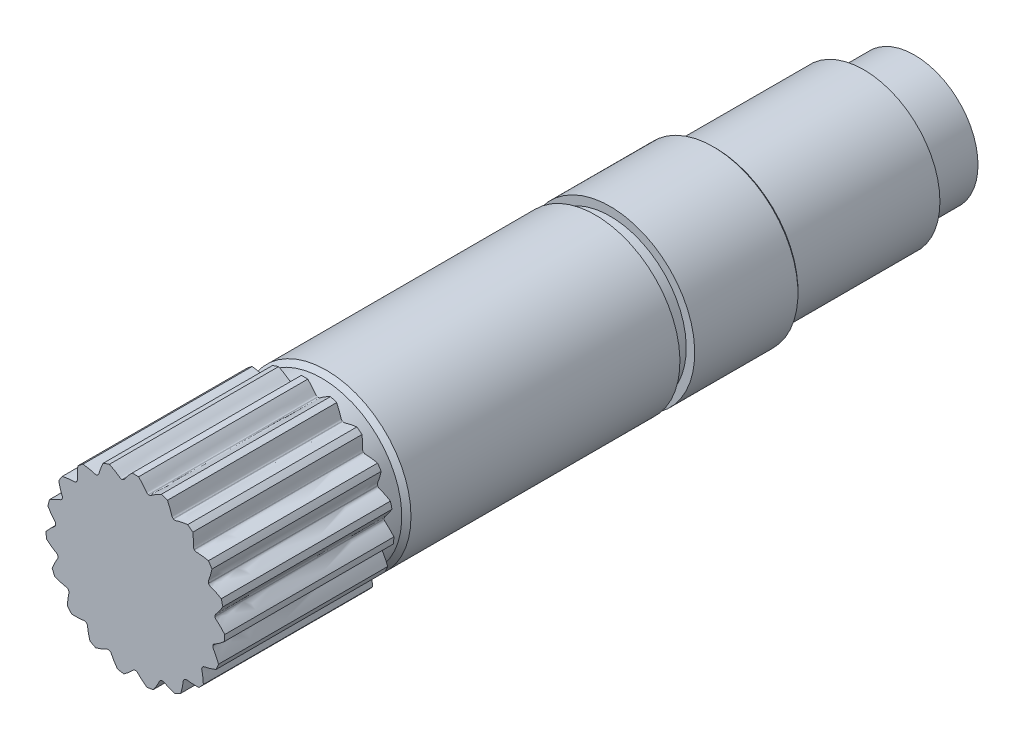
SolidWorks part; units mm, degrees
material "Alloy Steel"
ref_plane "Front Plane" through (0, 0, 0) normal (0, 0, 1) x (1, 0, 0)
ref_plane "Top Plane" through (0, 0, 0) normal (0, 1, 0) x (1, 0, 0)
ref_plane "Right Plane" through (0, 0, 0) normal (1, 0, 0) x (0, 0, -1)
sketch "Sketch12" plane through (0, 0, 0) normal (0, 0, 1) x (1, 0, 0)
  circle A0 centre (0, 0) radius 10
  dimension "D1" = 20
extrude "Shaft" add sketch "Sketch12" along normal mid plane 43
sketch "Sketch13" plane through (0, 0, 21.5) normal (0, 0, 1) x (1, 0, 0)
  circle A0 centre (0, 0) radius 9.4556
  dimension "D1" = 18.9113
extrude "Motor side relief" add sketch "Sketch13" along normal blind 1.587
sketch "Sketch14" plane through (0, 0, -21.5) normal (0, 0, -1) x (-1, 0, 0)
  circle A0 centre (0, 0) radius 8.3981
  dimension "D1" = 16.7963
sketch "Sketch15" plane through (0, 0, 23.087) normal (0, 0, 1) x (1, 0, 0)
  line L0 (5.7898, -7.4758) -> (5.8078, -7.4618)
  line L1 (5.8078, -7.4618) -> (5.8257, -7.4478)
  line L2 (7.9035, -5.1908) -> (7.9159, -5.1717)
  line L3 (7.9159, -5.1717) -> (7.9284, -5.1527)
  line L4 (9.1607, -2.3432) -> (9.1663, -2.3212)
  line L5 (9.1663, -2.3212) -> (9.1719, -2.2992)
  line L6 (9.4252, 0.7582) -> (9.4233, 0.7808)
  line L7 (9.4233, 0.7808) -> (9.4214, 0.8035)
  line L8 (8.6683, 3.7775) -> (8.6592, 3.7983)
  line L9 (8.6592, 3.7983) -> (8.6501, 3.8191)
  line L10 (6.9721, 6.3874) -> (6.9567, 6.4041)
  line L11 (6.9567, 6.4041) -> (6.9413, 6.4208)
  line L12 (4.5204, 8.3051) -> (4.5004, 8.316)
  line L13 (4.5004, 8.316) -> (4.4804, 8.3268)
  line L14 (1.5788, 9.3229) -> (1.5563, 9.3267)
  line L15 (1.5563, 9.3267) -> (1.5339, 9.3304)
  line L16 (-1.5339, 9.3304) -> (-1.5563, 9.3267)
  line L17 (-1.5563, 9.3267) -> (-1.5788, 9.3229)
  line L18 (-4.4804, 8.3268) -> (-4.5004, 8.316)
  line L19 (-4.5004, 8.316) -> (-4.5204, 8.3051)
  line L20 (-6.9413, 6.4208) -> (-6.9567, 6.4041)
  line L21 (-6.9567, 6.4041) -> (-6.9721, 6.3874)
  line L22 (-8.6501, 3.8191) -> (-8.6592, 3.7983)
  line L23 (-8.6592, 3.7983) -> (-8.6683, 3.7775)
  line L24 (-9.4214, 0.8035) -> (-9.4233, 0.7808)
  line L25 (-9.4233, 0.7808) -> (-9.4252, 0.7582)
  line L26 (-9.1719, -2.2992) -> (-9.1663, -2.3212)
  line L27 (-9.1663, -2.3212) -> (-9.1607, -2.3432)
  line L28 (-7.9284, -5.1527) -> (-7.9159, -5.1717)
  line L29 (-7.9159, -5.1717) -> (-7.9035, -5.1908)
  line L30 (-5.8257, -7.4478) -> (-5.8078, -7.4618)
  line L31 (-5.8078, -7.4618) -> (-5.7898, -7.4758)
  line L32 (-3.0917, -8.9359) -> (-3.0702, -8.9433)
  line L33 (-3.0702, -8.9433) -> (-3.0487, -8.9507)
  line L34 (-0.0227, -9.4556) -> (0, -9.4556)
  line L35 (0, -9.4556) -> (0.0227, -9.4556)
  line L36 (3.0487, -8.9507) -> (3.0702, -8.9433)
  line L37 (3.0702, -8.9433) -> (3.0917, -8.9359)
  arc A0 (4.6925, -9.4774) -> (5.3676, -9.1121) centre (0, 0) ccw
  arc A1 (7.5156, -7.4402) -> (8.0355, -6.8755) centre (0, 0) ccw
  arc A2 (9.5242, -4.5968) -> (9.8326, -3.8939) centre (0, 0) ccw
  arc A3 (10.5007, -1.2552) -> (10.5641, -0.4903) centre (0, 0) ccw
  arc A4 (10.3394, 2.2224) -> (10.1509, 2.9665) centre (0, 0) ccw
  arc A5 (9.0575, 5.4591) -> (8.6377, 6.1017) centre (0, 0) ccw
  arc A6 (6.7942, 8.1043) -> (6.1885, 8.5758) centre (0, 0) ccw
  arc A7 (3.7946, 9.8713) -> (3.0686, 10.1205) centre (0, 0) ccw
  arc A8 (0.3838, 10.5685) -> (-0.3838, 10.5685) centre (0, 0) ccw
  arc A9 (-3.0686, 10.1205) -> (-3.7946, 9.8713) centre (0, 0) ccw
  arc A10 (-6.1885, 8.5758) -> (-6.7942, 8.1043) centre (0, 0) ccw
  arc A11 (-8.6377, 6.1017) -> (-9.0575, 5.4591) centre (0, 0) ccw
  arc A12 (-10.1509, 2.9665) -> (-10.3394, 2.2224) centre (0, 0) ccw
  arc A13 (-10.5641, -0.4903) -> (-10.5007, -1.2552) centre (0, 0) ccw
  arc A14 (-9.8326, -3.8939) -> (-9.5242, -4.5968) centre (0, 0) ccw
  arc A15 (-8.0355, -6.8755) -> (-7.5156, -7.4402) centre (0, 0) ccw
  arc A16 (-5.3676, -9.1121) -> (-4.6925, -9.4774) centre (0, 0) ccw
  arc A17 (-2.1181, -10.3612) -> (-1.361, -10.4876) centre (0, 0) ccw
  arc A18 (1.361, -10.4876) -> (2.1181, -10.3612) centre (0, 0) ccw
  spline S0 degree 3 poles (3.0917, -8.9359) (3.1544, -8.9142) (3.2184, -8.911) (3.3396, -8.938) (3.397, -8.9729) (3.5767, -9.0624) (3.828, -9.1783) (4.24, -9.3384) (4.5379, -9.4334) (4.6925, -9.4774) knots 0 0 0 0 0.125 0.125 0.25 0.25 0.5 0.75 1 1 1 1
  spline S1 degree 3 poles (5.3676, -9.1121) (5.4153, -8.9586) (5.4987, -8.6572) (5.5901, -8.2247) (5.6305, -7.951) (5.6538, -7.7516) (5.656, -7.6845) (5.6997, -7.5682) (5.7374, -7.5164) (5.7898, -7.4758) knots 0 0 0 0 0.25 0.5 0.75 0.75 0.875 0.875 1 1 1 1
  spline S2 degree 3 poles (5.8257, -7.4478) (5.8779, -7.407) (5.9374, -7.3832) (6.0608, -7.3694) (6.1265, -7.3837) (6.3255, -7.41) (6.6008, -7.438) (7.0425, -7.4557) (7.3551, -7.4488) (7.5156, -7.4402) knots 0 0 0 0 0.125 0.125 0.25 0.25 0.5 0.75 1 1 1 1
  spline S3 degree 3 poles (8.0355, -6.8755) (8.0308, -6.7148) (8.0117, -6.4027) (7.9577, -5.964) (7.9071, -5.692) (7.8645, -5.4958) (7.8447, -5.4316) (7.8483, -5.3075) (7.8671, -5.2462) (7.9035, -5.1908) knots 0 0 0 0 0.25 0.5 0.75 0.75 0.875 0.875 1 1 1 1
  spline S4 degree 3 poles (7.9284, -5.1527) (7.9645, -5.0971) (8.013, -5.0552) (8.1253, -5.0021) (8.192, -4.9944) (8.3888, -4.9546) (8.6583, -4.8918) (9.0817, -4.765) (9.3752, -4.6571) (9.5242, -4.5968) knots 0 0 0 0 0.125 0.125 0.25 0.25 0.5 0.75 1 1 1 1
  spline S5 degree 3 poles (9.8326, -3.8939) (9.7759, -3.7434) (9.6566, -3.4544) (9.4631, -3.057) (9.3268, -2.8161) (9.2228, -2.6445) (9.1833, -2.5901) (9.1463, -2.4716) (9.1443, -2.4075) (9.1607, -2.3432) knots 0 0 0 0 0.25 0.5 0.75 0.75 0.875 0.875 1 1 1 1
  spline S6 degree 3 poles (9.1719, -2.2992) (9.188, -2.2349) (9.2203, -2.1795) (9.3092, -2.0928) (9.3699, -2.0638) (9.543, -1.9624) (9.7775, -1.8154) (10.1368, -1.558) (10.3793, -1.3606) (10.5007, -1.2552) knots 0 0 0 0 0.125 0.125 0.25 0.25 0.5 0.75 1 1 1 1
  spline S7 degree 3 poles (10.5641, -0.4903) (10.4617, -0.3663) (10.255, -0.1317) (9.9429, 0.1813) (9.7359, 0.3649) (9.5818, 0.4935) (9.5267, 0.532) (9.4533, 0.6322) (9.4305, 0.6921) (9.4252, 0.7582) knots 0 0 0 0 0.25 0.5 0.75 0.75 0.875 0.875 1 1 1 1
  spline S8 degree 3 poles (9.4214, 0.8035) (9.4158, 0.8695) (9.4284, 0.9324) (9.4844, 1.0433) (9.5323, 1.0904) (9.6631, 1.2426) (9.8372, 1.4577) (10.0935, 1.8179) (10.2588, 2.0833) (10.3394, 2.2224) knots 0 0 0 0 0.125 0.125 0.25 0.25 0.5 0.75 1 1 1 1
  spline S9 degree 3 poles (10.1509, 2.9665) (10.0138, 3.0504) (9.7422, 3.2052) (9.3453, 3.4) (9.0899, 3.5063) (8.9024, 3.5779) (8.8378, 3.5965) (8.7358, 3.6674) (8.6948, 3.7167) (8.6683, 3.7775) knots 0 0 0 0 0.25 0.5 0.75 0.75 0.875 0.875 1 1 1 1
  spline S10 degree 3 poles (8.6501, 3.8191) (8.6233, 3.8797) (8.6148, 3.9433) (8.6317, 4.0663) (8.6618, 4.1264) (8.7361, 4.3129) (8.8308, 4.5729) (8.9563, 4.9967) (9.0265, 5.3014) (9.0575, 5.4591) knots 0 0 0 0 0.125 0.125 0.25 0.25 0.5 0.75 1 1 1 1
  spline S11 degree 3 poles (8.6377, 6.1017) (8.4808, 6.1366) (8.1736, 6.1948) (7.735, 6.2502) (7.4588, 6.2678) (7.2583, 6.2747) (7.1911, 6.2713) (7.0717, 6.3052) (7.0169, 6.3385) (6.9721, 6.3874) knots 0 0 0 0 0.25 0.5 0.75 0.75 0.875 0.875 1 1 1 1
  spline S12 degree 3 poles (6.9413, 6.4208) (6.8963, 6.4695) (6.8676, 6.5268) (6.8437, 6.6487) (6.8526, 6.7153) (6.8624, 6.9158) (6.8676, 7.1925) (6.8486, 7.6341) (6.816, 7.9451) (6.7942, 8.1043) knots 0 0 0 0 0.125 0.125 0.25 0.25 0.5 0.75 1 1 1 1
  spline S13 degree 3 poles (6.1885, 8.5758) (6.0287, 8.5578) (5.7193, 8.5131) (5.2865, 8.4231) (5.0196, 8.3501) (4.8276, 8.2914) (4.7652, 8.2664) (4.6412, 8.2597) (4.5786, 8.2734) (4.5204, 8.3051) knots 0 0 0 0 0.25 0.5 0.75 0.75 0.875 0.875 1 1 1 1
  spline S14 degree 3 poles (4.4804, 8.3268) (4.422, 8.3582) (4.3763, 8.4031) (4.3141, 8.5106) (4.3009, 8.5765) (4.245, 8.7693) (4.1601, 9.0326) (3.9988, 9.4442) (3.8669, 9.7277) (3.7946, 9.8713) knots 0 0 0 0 0.125 0.125 0.25 0.25 0.5 0.75 1 1 1 1
  spline S15 degree 3 poles (3.0686, 10.1205) (2.9233, 10.0517) (2.6452, 9.9089) (2.2651, 9.6832) (2.0363, 9.5275) (1.8738, 9.4097) (1.8229, 9.3658) (1.7078, 9.3192) (1.6441, 9.3118) (1.5788, 9.3229) knots 0 0 0 0 0.25 0.5 0.75 0.75 0.875 0.875 1 1 1 1
  spline S16 degree 3 poles (1.5339, 9.3304) (1.4685, 9.3411) (1.4107, 9.3688) (1.3169, 9.4502) (1.283, 9.5083) (1.1676, 9.6725) (1.0018, 9.894) (0.7156, 10.2309) (0.4988, 10.4563) (0.3838, 10.5685) knots 0 0 0 0 0.125 0.125 0.25 0.25 0.5 0.75 1 1 1 1
  spline S17 degree 3 poles (-0.3838, 10.5685) (-0.4988, 10.4563) (-0.7156, 10.2309) (-1.0018, 9.894) (-1.1676, 9.6725) (-1.283, 9.5083) (-1.3169, 9.4502) (-1.4107, 9.3688) (-1.4685, 9.3411) (-1.5339, 9.3304) knots 0 0 0 0 0.25 0.5 0.75 0.75 0.875 0.875 1 1 1 1
  spline S18 degree 3 poles (-1.5788, 9.3229) (-1.6441, 9.3118) (-1.7078, 9.3192) (-1.8229, 9.3658) (-1.8738, 9.4097) (-2.0363, 9.5275) (-2.2651, 9.6832) (-2.6452, 9.9089) (-2.9233, 10.0517) (-3.0686, 10.1205) knots 0 0 0 0 0.125 0.125 0.25 0.25 0.5 0.75 1 1 1 1
  spline S19 degree 3 poles (-3.7946, 9.8713) (-3.8669, 9.7277) (-3.9988, 9.4442) (-4.1601, 9.0326) (-4.245, 8.7693) (-4.3009, 8.5765) (-4.3141, 8.5106) (-4.3763, 8.4031) (-4.422, 8.3582) (-4.4804, 8.3268) knots 0 0 0 0 0.25 0.5 0.75 0.75 0.875 0.875 1 1 1 1
  spline S20 degree 3 poles (-4.5204, 8.3051) (-4.5786, 8.2734) (-4.6412, 8.2597) (-4.7652, 8.2664) (-4.8276, 8.2914) (-5.0196, 8.3501) (-5.2865, 8.4231) (-5.7193, 8.5131) (-6.0287, 8.5578) (-6.1885, 8.5758) knots 0 0 0 0 0.125 0.125 0.25 0.25 0.5 0.75 1 1 1 1
  spline S21 degree 3 poles (-6.7942, 8.1043) (-6.816, 7.9451) (-6.8486, 7.6341) (-6.8676, 7.1925) (-6.8624, 6.9158) (-6.8526, 6.7153) (-6.8437, 6.6487) (-6.8676, 6.5268) (-6.8963, 6.4695) (-6.9413, 6.4208) knots 0 0 0 0 0.25 0.5 0.75 0.75 0.875 0.875 1 1 1 1
  spline S22 degree 3 poles (-6.9721, 6.3874) (-7.0169, 6.3385) (-7.0717, 6.3052) (-7.1911, 6.2713) (-7.2583, 6.2747) (-7.4588, 6.2678) (-7.735, 6.2502) (-8.1736, 6.1948) (-8.4808, 6.1366) (-8.6377, 6.1017) knots 0 0 0 0 0.125 0.125 0.25 0.25 0.5 0.75 1 1 1 1
  spline S23 degree 3 poles (-9.0575, 5.4591) (-9.0265, 5.3014) (-8.9563, 4.9967) (-8.8308, 4.5729) (-8.7361, 4.3129) (-8.6618, 4.1264) (-8.6317, 4.0663) (-8.6148, 3.9433) (-8.6233, 3.8797) (-8.6501, 3.8191) knots 0 0 0 0 0.25 0.5 0.75 0.75 0.875 0.875 1 1 1 1
  spline S24 degree 3 poles (-8.6683, 3.7775) (-8.6948, 3.7167) (-8.7358, 3.6674) (-8.8378, 3.5965) (-8.9024, 3.5779) (-9.0899, 3.5063) (-9.3453, 3.4) (-9.7422, 3.2052) (-10.0138, 3.0504) (-10.1509, 2.9665) knots 0 0 0 0 0.125 0.125 0.25 0.25 0.5 0.75 1 1 1 1
  spline S25 degree 3 poles (-10.3394, 2.2224) (-10.2588, 2.0833) (-10.0935, 1.8179) (-9.8372, 1.4577) (-9.6631, 1.2426) (-9.5323, 1.0904) (-9.4844, 1.0433) (-9.4284, 0.9324) (-9.4158, 0.8695) (-9.4214, 0.8035) knots 0 0 0 0 0.25 0.5 0.75 0.75 0.875 0.875 1 1 1 1
  spline S26 degree 3 poles (-9.4252, 0.7582) (-9.4305, 0.6921) (-9.4533, 0.6322) (-9.5267, 0.532) (-9.5818, 0.4935) (-9.7359, 0.3649) (-9.9429, 0.1813) (-10.255, -0.1317) (-10.4617, -0.3663) (-10.5641, -0.4903) knots 0 0 0 0 0.125 0.125 0.25 0.25 0.5 0.75 1 1 1 1
  spline S27 degree 3 poles (-10.5007, -1.2552) (-10.3793, -1.3606) (-10.1368, -1.558) (-9.7775, -1.8154) (-9.543, -1.9624) (-9.3699, -2.0638) (-9.3092, -2.0928) (-9.2203, -2.1795) (-9.188, -2.2349) (-9.1719, -2.2992) knots 0 0 0 0 0.25 0.5 0.75 0.75 0.875 0.875 1 1 1 1
  spline S28 degree 3 poles (-9.1607, -2.3432) (-9.1443, -2.4075) (-9.1463, -2.4716) (-9.1833, -2.5901) (-9.2228, -2.6445) (-9.3268, -2.8161) (-9.4631, -3.057) (-9.6566, -3.4544) (-9.7759, -3.7434) (-9.8326, -3.8939) knots 0 0 0 0 0.125 0.125 0.25 0.25 0.5 0.75 1 1 1 1
  spline S29 degree 3 poles (-9.5242, -4.5968) (-9.3752, -4.6571) (-9.0817, -4.765) (-8.6583, -4.8918) (-8.3888, -4.9546) (-8.192, -4.9944) (-8.1253, -5.0021) (-8.013, -5.0552) (-7.9645, -5.0971) (-7.9284, -5.1527) knots 0 0 0 0 0.25 0.5 0.75 0.75 0.875 0.875 1 1 1 1
  spline S30 degree 3 poles (-7.9035, -5.1908) (-7.8671, -5.2462) (-7.8483, -5.3075) (-7.8447, -5.4316) (-7.8645, -5.4958) (-7.9071, -5.692) (-7.9577, -5.964) (-8.0117, -6.4027) (-8.0308, -6.7148) (-8.0355, -6.8755) knots 0 0 0 0 0.125 0.125 0.25 0.25 0.5 0.75 1 1 1 1
  spline S31 degree 3 poles (-7.5156, -7.4402) (-7.3551, -7.4488) (-7.0425, -7.4557) (-6.6008, -7.438) (-6.3255, -7.41) (-6.1265, -7.3837) (-6.0608, -7.3694) (-5.9374, -7.3832) (-5.8779, -7.407) (-5.8257, -7.4478) knots 0 0 0 0 0.25 0.5 0.75 0.75 0.875 0.875 1 1 1 1
  spline S32 degree 3 poles (-5.7898, -7.4758) (-5.7374, -7.5164) (-5.6997, -7.5682) (-5.656, -7.6845) (-5.6538, -7.7516) (-5.6305, -7.951) (-5.5901, -8.2247) (-5.4987, -8.6572) (-5.4153, -8.9586) (-5.3676, -9.1121) knots 0 0 0 0 0.125 0.125 0.25 0.25 0.5 0.75 1 1 1 1
  spline S33 degree 3 poles (-4.6925, -9.4774) (-4.5379, -9.4334) (-4.24, -9.3384) (-3.828, -9.1783) (-3.5767, -9.0624) (-3.397, -8.9729) (-3.3396, -8.938) (-3.2184, -8.911) (-3.1544, -8.9142) (-3.0917, -8.9359) knots 0 0 0 0 0.25 0.5 0.75 0.75 0.875 0.875 1 1 1 1
  spline S34 degree 3 poles (-3.0487, -8.9507) (-2.986, -8.972) (-2.9335, -9.0088) (-2.8544, -9.1046) (-2.8306, -9.1674) (-2.7437, -9.3484) (-2.6166, -9.5942) (-2.3898, -9.9736) (-2.2131, -10.2315) (-2.1181, -10.3612) knots 0 0 0 0 0.125 0.125 0.25 0.25 0.5 0.75 1 1 1 1
  spline S35 degree 3 poles (-1.361, -10.4876) (-1.229, -10.3957) (-0.9781, -10.2091) (-0.6404, -9.9239) (-0.4404, -9.7327) (-0.2995, -9.5898) (-0.2565, -9.5381) (-0.1506, -9.4732) (-0.089, -9.4555) (-0.0227, -9.4556) knots 0 0 0 0 0.25 0.5 0.75 0.75 0.875 0.875 1 1 1 1
  spline S36 degree 3 poles (0.0227, -9.4556) (0.089, -9.4555) (0.1506, -9.4732) (0.2565, -9.5381) (0.2995, -9.5898) (0.4404, -9.7327) (0.6404, -9.9239) (0.9781, -10.2091) (1.229, -10.3957) (1.361, -10.4876) knots 0 0 0 0 0.125 0.125 0.25 0.25 0.5 0.75 1 1 1 1
  spline S37 degree 3 poles (2.1181, -10.3612) (2.2131, -10.2315) (2.3898, -9.9736) (2.6166, -9.5942) (2.7437, -9.3484) (2.8306, -9.1674) (2.8544, -9.1046) (2.9335, -9.0088) (2.986, -8.972) (3.0487, -8.9507) knots 0 0 0 0 0.25 0.5 0.75 0.75 0.875 0.875 1 1 1 1
extrude "Motor spline" add sketch "Sketch15" along normal blind 20
chamfer "Chamfer3" distance 1 angle 45 1 edges at (10, 0, 21.5)
sketch "Sketch23" plane through (0, 0, -31.5) normal (-0.948, 0.3182, 0) x (-0.3182, -0.948, 0)
  line L0 (10, 20.2042) -> (9, 20.2042)
  line L1 (9, 20.2042) -> (9, 18.4542)
  line L2 (9, 18.4542) -> (10, 18.4542)
  line L3 (10, 18.4542) -> (10, 20.2042)
  line L4 (10, 10) -> (10, 52) construction
  line L5 (-13.85, 20.2042) -> (13.85, 20.2042) construction
  line L7 (0, 185.3358) -> (0, -121.609) construction
  dimension "D1" = 1.75
  dimension "D2" = 1
revolve "snap ring" cut sketch "Sketch23" angle 360 about L7
sketch "Sketch24" plane through (0, 0, 0) normal (0, 1, 0) x (1, 0, 0)
  line L3 (10, 21.5) -> (10, 25.5)
  line L5 (7.5, 43.5) -> (7.5, 49.5)
  line L6 (7.5, 49.5) -> (0, 49.5)
  line L7 (0, 49.5) -> (0, 21.5)
  line L8 (10, 21.5) -> (-10, 21.5) construction
  line L9 (0, 21.5) -> (10, 21.5)
  line L10 (0, 0) -> (0, 49.7252) construction
  line L12 (7.5, 43.5) -> (9, 43.5)
  line L14 (10, 25.5) -> (9, 25.5)
  line L15 (9, 25.5) -> (9, 43.5)
  dimension "D1" = 15
  dimension "D2" = 22
  dimension "D3" = 4
  dimension "D8" = 6
revolve "Revolve1" add sketch "Sketch24" angle 360 about L10
chamfer "Chamfer4" distance 1 angle 25 2 edges at (9, 0, -43.5) (7.5, 0, -49.5) first distance on face at (7.5, 0, -43.5) first distance on face at (7.5, 0, -49.5)
chamfer "Chamfer5" distance 0.25 angle 45 1 edges at (10, 0, -25.5)
